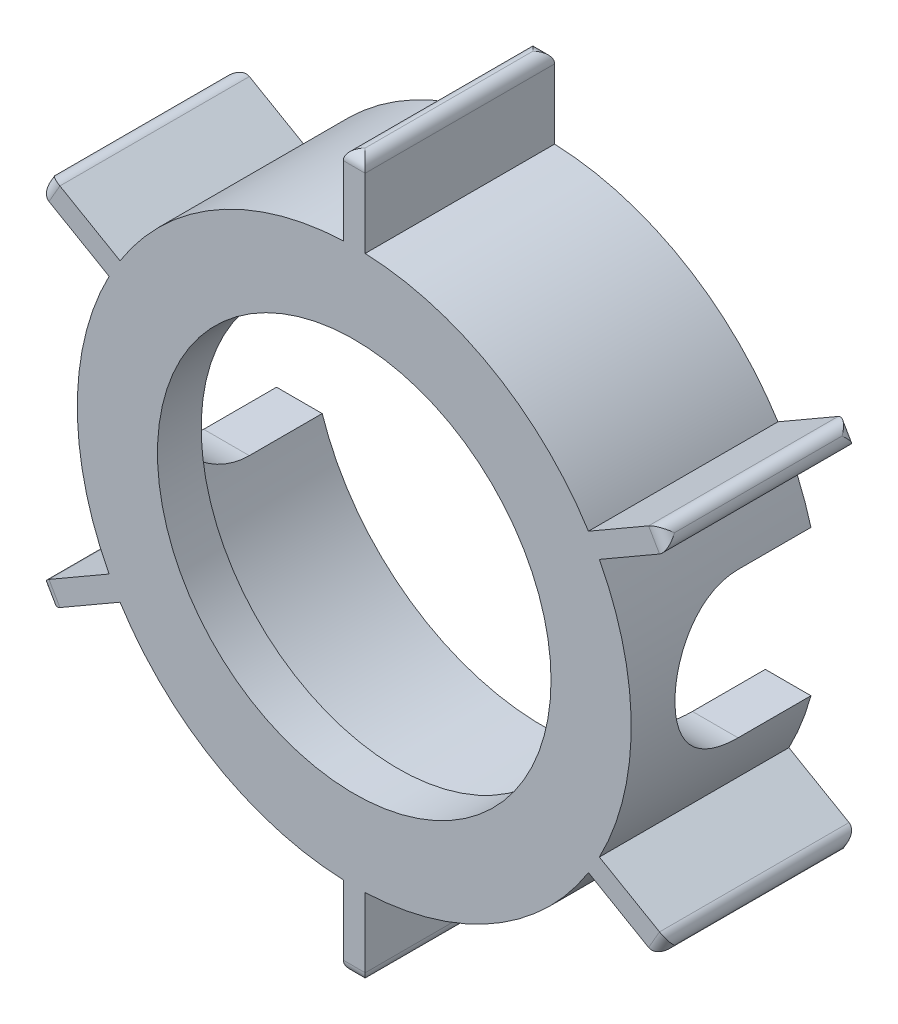
SolidWorks part; units mm, degrees
ref_plane "Plan de face" through (0, 0, 0) normal (0, 0, 1) x (1, 0, 0)
ref_plane "Plan de dessus" through (0, 0, 0) normal (0, 1, 0) x (1, 0, 0)
ref_plane "Plan de droite" through (0, 0, 0) normal (1, 0, 0) x (0, 0, -1)
sketch "Contour" plane through (0, 0, 0) normal (0, 0, 1) x (1, 0, 0)
  circle A0 centre (0, 0) radius 19
  dimension "D1" = 38
extrude "Boss.-Extru.1_Contour" add sketch "Contour" along normal blind 13
shell "Coque1" thickness 3 removed face at (19, 0, 0)
ref_plane "Plan1_Aimants" through (19, 0, 0) normal (1, 0, 0) x (0, 0, -1)
sketch "Ouvertue_aimant" plane through (19, 0, 0) normal (1, 0, 0) x (0, 0, -1)
  line L0 (-5, 5) -> (0, 5) construction
  line L6 (-10, 0) -> (0, 0) construction
  line L7 (-10, -16) -> (-10, 16) construction
  line L9 (0, -19) -> (0, 19) construction
  line L13 (-5, -5) -> (0, -5) construction
  line L14 (0, 5) -> (-5, 5)
  line L15 (-5, -5) -> (0, -5)
  line L16 (0, -5) -> (0, 5)
  circle A4 centre (-5, 0) radius 5 construction
  arc A5 (-5, 5) -> (-5, -5) centre (-5, 0) ccw
  dimension "D1" = 10
extrude "Enlèv. mat.-Extru.1_Ouvertue_aimant" cut sketch "Ouvertue_aimant" against normal up to next
mirror "Symétrie1_Ouvertue_aimant" about plane through (0, 0, 0) normal (1, 0, 0) of "Enlèv. mat.-Extru.1_Ouvertue_aimant"
sketch "Ouverture_Écrou" plane through (0, 0, 13) normal (0, 0, 1) x (1, 0, 0)
  circle A0 centre (0, 0) radius 13.5
  dimension "D1" = 27
extrude "Enlèv. mat.-Extru.2_Ouverture_Écrou" cut sketch "Ouverture_Écrou" against normal up to next
ref_axis "Axe1" through (0, 0, 13.65) along (0, 0, -1)
ref_plane "Plan1" through (0, 24.5, 0) normal (0, 1, 0) x (1, 0, 0)
sketch "Ailettes" plane through (0, 24.5, 0) normal (0, 1, 0) x (1, 0, 0)
  line L0 (-20.9, 0) -> (20.9, 0) construction
  line L1 (-0.75, 0) -> (0.75, 0)
  line L2 (-0.75, 0) -> (-0.75, -13)
  line L3 (-0.75, -13) -> (0.75, -13)
  line L4 (0.75, 0) -> (0.75, -13)
  line L5 (-0.75, 0) -> (0.75, -13) construction
  line L6 (-0.75, -13) -> (0.75, 0) construction
  line L7 (-19, -13) -> (19, -13) construction
  line L8 (0, -7.15) -> (0, 7.15) construction
  point P4 (0, -6.5)
  dimension "D1" = 1.5
extrude "Boss.-Extru.2_Ailettes" add sketch "Ailettes" against normal up to next
pattern_circular "Répétition circulaire4_Ailettes" count 6 over 360 about axis through (0, 0, 13) along (0, 0, -1) of "Boss.-Extru.2_Ailettes"
fillet "Congé1_Ailettes" radius 0.75 24 edges at (-20.8426, -12.8995, 6.5) (-21.2176, -12.25, 13) (-21.5926, -11.6005, 6.5) (-21.2176, -12.25, 0) (-21.5926, 11.6005, 6.5) (-21.2176, 12.25, 13) (-20.8426, 12.8995, 6.5) (-21.2176, 12.25, 0) (-0.75, 24.5, 6.5) (0, 24.5, 13) (0.75, 24.5, 6.5) (0, 24.5, 0) (20.8426, 12.8995, 6.5) (21.2176, 12.25, 13) (21.5926, 11.6005, 6.5) (21.2176, 12.25, 0) (21.5926, -11.6005, 6.5) (21.2176, -12.25, 13) (20.8426, -12.8995, 6.5) (21.2176, -12.25, 0) (0.75, -24.5, 6.5) (0, -24.5, 13) (-0.75, -24.5, 6.5) (0, -24.5, 0)
sketch "Esquisse1" plane through (0, 0, 0) normal (0, 0, -1) x (-1, 0, 0)
  line L0 (0, 24.5) -> (0, -24.5) construction
equation "\"D1@Congé1_Ailettes\"=1.5 / 2"
